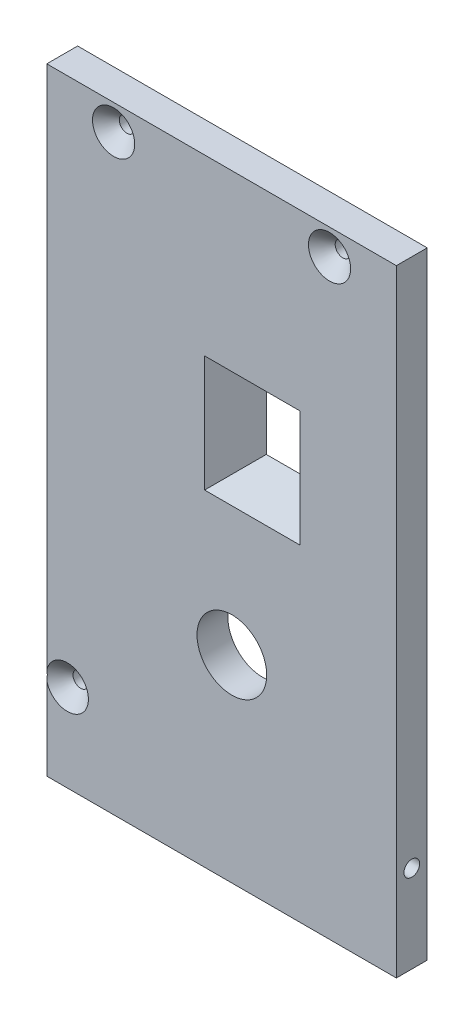
SolidWorks part; units mm, degrees
ref_plane "Front Plane" through (0, 0, 0) normal (0, 0, 1) x (1, 0, 0)
ref_plane "Top Plane" through (0, 0, 0) normal (0, 1, 0) x (1, 0, 0)
ref_plane "Right Plane" through (0, 0, 0) normal (1, 0, 0) x (0, 0, -1)
sketch "Sketch1" plane through (0, 0, 0) normal (0, 0, 1) x (1, 0, 0)
  line L1 (-17, -30) -> (17, -30)
  line L2 (-17, -30) -> (-17, 30)
  line L3 (-17, 30) -> (17, 30)
  line L4 (17, -30) -> (17, 30)
  line L5 (-17, -30) -> (17, 30) construction
  line L6 (-17, 30) -> (17, -30) construction
  line L7 (0, 0) -> (0, 18.7389) construction
  circle A1 centre (-15, -21.5) radius 0.75
  circle A2 centre (-10.5, 27.5) radius 0.75
  circle A3 centre (10.5, 27.5) radius 0.75
  point P0 (0, 0)
  dimension "D4" = 1.5
  dimension "D10" = 2.5
  dimension "D1" = 60
  dimension "D2" = 34
  dimension "D5" = 2
  dimension "D6" = 8.5
  dimension "D7" = 6.5
  dimension "D8" = 6.5
  dimension "D9" = 2.5
extrude "Boss-Extrude1" add sketch "Sketch1" along normal blind 3
chamfer "Chamfer1" distance 1.3 angle 45 3 edges at (-14.25, -21.5, 3) (11.25, 27.5, 3) (-11.25, 27.5, 3)
sketch "Sketch2" plane through (17, 0, 0) normal (1, 0, 0) x (0, 0, -1)
  line L0 (-3, -30) -> (0, -30) construction
  line L1 (0, -30) -> (0, 30) construction
  circle A0 centre (-1.5, -21.5) radius 0.762
  dimension "D3" = 1.524
  dimension "D1" = 8.5
  dimension "D2" = 1.5
extrude "Cut-Extrude1" cut sketch "Sketch2" against normal blind 7
sketch "Sketch3" plane through (0, 0, 0) normal (0, 0, -1) x (-1, 0, 0)
  line L0 (17, -30) -> (-17, -30) construction
  line L1 (12, -30) -> (3.7653, -30)
  line L2 (12, -30) -> (12, -24.8)
  line L3 (12, -24.8) -> (3.7653, -24.8)
  line L4 (3.7653, -30) -> (3.7653, -24.8)
  line L5 (17, 30) -> (17, -30) construction
  line L6 (12, -24.8) -> (7, -24.8)
  line L7 (12, -24.8) -> (12, -20.4)
  line L8 (12, -20.4) -> (7, -20.4)
  line L9 (7, -24.8) -> (7, -20.4)
  point P9 (12, -27.4)
  line M7 (-17, -30) -> (17, -30)
  dimension "D1" = 5
  dimension "D2" = 5.2
  dimension "D3" = 4.4
  dimension "D4" = 5
extrude "Cut-Extrude2" cut sketch "Sketch3" against normal blind 1.7 contours L4 L2 L3 M7 | L9 L3 L7 L8 region at (-7.8827, -27.4, 0) region at (-9.5, -22.6, 0)
sketch "Sketch4" plane through (0, -30, 0) normal (0, -1, 0) x (1, 0, 0)
  line L0 (-17, 3) -> (17, 3) construction
  line L1 (17, 3) -> (17, 0) construction
  circle A0 centre (15, 1.5) radius 0.762
  dimension "D1" = 1.524
  dimension "D2" = 1.5
  dimension "D3" = 2
extrude "Cut-Extrude3" cut sketch "Sketch4" against normal blind 7
sketch "Sketch5" plane through (0, 0, 0) normal (0, 0, -1) x (-1, 0, 0)
  line L1 (-16.5, 21) -> (10.5, 21)
  line L2 (-16.5, 21) -> (-16.5, -6.15)
  line L3 (-16.5, -6.15) -> (10.5, -6.15)
  line L4 (10.5, 21) -> (10.5, -6.15)
  line L5 (-17, 30) -> (17, 30) construction
  line L6 (-17, -30) -> (-17, 30) construction
  line L8 (-4.65, 10.075) -> (-1.35, 10.075)
  line L9 (-4.65, 10.075) -> (-4.65, 4.775)
  line L10 (-4.65, 4.775) -> (-1.35, 4.775)
  line L11 (-1.35, 10.075) -> (-1.35, 4.775)
  point P9 (-3, 21)
  dimension "D1" = 27.15
  dimension "D2" = 27
  dimension "D3" = 9
  dimension "D4" = 5.3
  dimension "D5" = 3.3
  dimension "D6" = 11.85
  dimension "D7" = 11.85
  dimension "D8" = 10.925
  dimension "D9" = 10.925
  dimension "D10" = 0.5
extrude "Cut-Extrude4" cut sketch "Sketch5" against normal blind 3.5 contours L11 L10 L9 L8
sketch "Sketch6" plane through (0, 0, 0) normal (0, 0, -1) x (-1, 0, 0)
  line L1 (-13.5, 21) -> (13.5, 21)
  line L2 (-13.5, 21) -> (-13.5, -6.15)
  line L3 (-13.5, -6.15) -> (13.5, -6.15)
  line L4 (13.5, 21) -> (13.5, -6.15)
  line L5 (-17, 30) -> (17, 30) construction
  line L6 (0, 30) -> (0, 24.642) construction
  line L7 (0, 21) -> (0, 12.844) construction
  dimension "D1" = 27.15
  dimension "D2" = 27
  dimension "D3" = 9
sketch "Sketch7" plane through (0, 0, 0) normal (0, 0, -1) x (-1, 0, 0)
  line L1 (0.5, 19.85) -> (-6.5, 19.85)
  line L2 (0.5, 19.85) -> (0.5, 14.55)
  line L3 (0.5, 14.55) -> (-6.5, 14.55)
  line L4 (-6.5, 19.85) -> (-6.5, 14.55)
  line L7 (-6.5, -5) -> (0.5, -5)
  line L8 (-6.5, -5) -> (-6.5, 0.3)
  line L9 (-6.5, 0.3) -> (0.5, 0.3)
  line L10 (0.5, -5) -> (0.5, 0.3)
  line L11 (-6.5, -5) -> (0.5, 0.3) construction
  line L12 (-6.5, 0.3) -> (0.5, -5) construction
  line L18 (-17, -30) -> (-17, 30) construction
  circle A0 centre (-13.25, 17.75) radius 0.762
  circle A1 centre (7.25, 17.75) radius 0.762
  circle A2 centre (7.25, -2.9) radius 0.762
  circle A3 centre (-13.25, -2.9) radius 0.762
  point P0 (0, 12.844)
  point P6 (-3, -2.35)
  dimension "D11" = 1.524
  dimension "D12" = 1.524
  dimension "D1" = 5.3
  dimension "D2" = 7
  dimension "D3" = 7
  dimension "D4" = 5.3
  dimension "D5" = 6.75
  dimension "D6" = 3.75
  dimension "D7" = 3.75
  dimension "D8" = 6.75
  dimension "D9" = 6.75
  dimension "D14" = 6.75
extrude "Cut-Extrude5" cut sketch "Sketch7" against normal blind 2.5
sketch "Sketch8" plane through (0, 0, 0) normal (0, 0, -1) x (-1, 0, 0)
  line L1 (7.9, 16.18) -> (9.7, 16.18)
  line L2 (7.9, 16.18) -> (7.9, -1.12)
  line L3 (7.9, -1.12) -> (9.7, -1.12)
  line L4 (9.7, 16.18) -> (9.7, -1.12)
  line L5 (-17, -30) -> (-17, 30) construction
  line L9 (-13.9, -1.12) -> (-15.7, -1.12)
  line L10 (-15.7, 16.18) -> (-15.7, -1.12)
  line L11 (-13.9, 16.18) -> (-15.7, 16.18)
  line L12 (-13.9, 16.18) -> (-13.9, -1.12)
  dimension "D1" = 1.8
  dimension "D2" = 17.3
  dimension "D3" = 21.8
  dimension "D4" = 1.3
extrude "Cut-Extrude6" cut sketch "Sketch8" against normal blind 2.5
sketch "Sketch9" plane through (0, 0, 0) normal (0, 0, -1) x (-1, 0, 0)
  line L0 (-1, -10.79) -> (-1, -7.4) construction
  line L1 (-13.5, -6.15) -> (13.5, -6.15) construction
  line L2 (17, 30) -> (17, -30) construction
  circle A0 centre (-1, -10.79) radius 3.39
  dimension "D1" = 6.78
  dimension "D2" = 18
  dimension "D3" = 1.25
extrude "Cut-Extrude7" cut sketch "Sketch9" against normal blind 7.5
chamfer "Chamfer2" distance 3 angle 45 4 edges at (4.65, 7.425, 3) (3, 4.775, 3) (1.35, 7.425, 3) (3, 10.075, 3)
